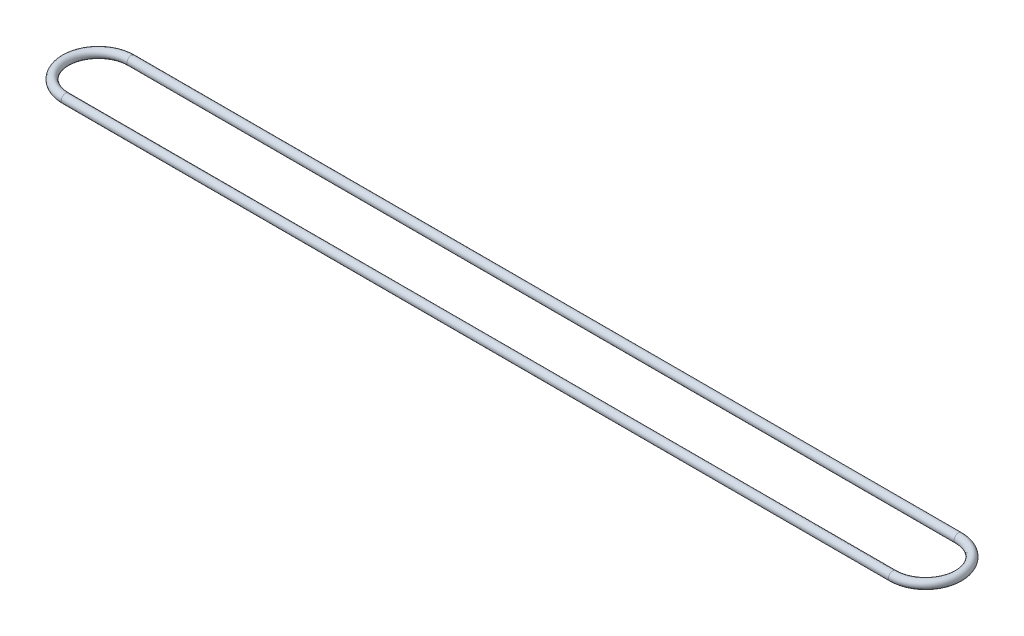
SolidWorks part; units mm, degrees
ref_plane "Front Plane" through (0, 0, 0) normal (0, 0, 1) x (1, 0, 0)
ref_plane "Top Plane" through (0, 0, 0) normal (0, 1, 0) x (1, 0, 0)
ref_plane "Right Plane" through (0, 0, 0) normal (1, 0, 0) x (0, 0, -1)
sketch "Sketch5" plane through (0, 0, 0) normal (0, 1, 0) x (1, 0, 0)
  line L0 (-506.5924, 0) -> (411.143, 0) construction
  line L1 (-506.5924, 36.4323) -> (411.143, 36.4323)
  line L2 (-506.5924, -36.4323) -> (411.143, -36.4323)
  arc A0 (-506.5924, 36.4323) -> (-506.5924, -36.4323) centre (-506.5924, 0) ccw
  arc A1 (411.143, -36.4323) -> (411.143, 36.4323) centre (411.143, 0) ccw
  point P3 (-47.7247, 0)
  point P8 (-543.0247, 0)
  point P9 (447.5753, 0)
  dimension "D2" = 72.8646
  dimension "D3" = 990.6
sweep "Sweep1" add path "Sketch5" circular profile diameter 9.525 parameters "D3"=9.525
